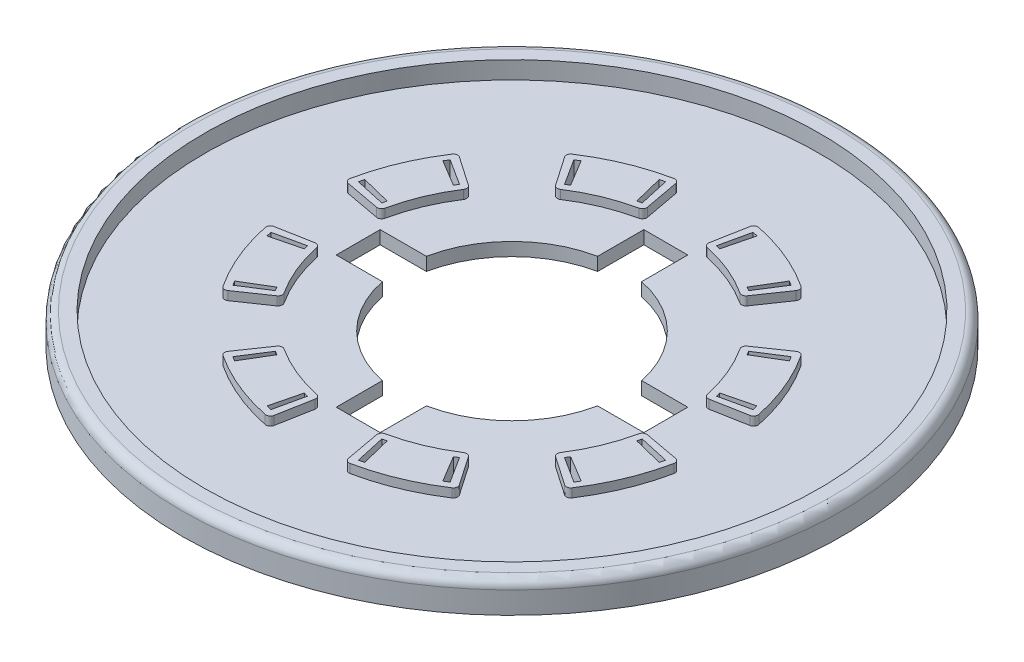
SolidWorks part; units mm, degrees
ref_plane "Alzado" through (0, 0, 0) normal (0, 0, 1) x (1, 0, 0)
ref_plane "Planta" through (0, 0, 0) normal (0, 1, 0) x (1, 0, 0)
ref_plane "Vista lateral" through (0, 0, 0) normal (1, 0, 0) x (0, 0, -1)
sketch "Croquis1" plane through (0, 0, 0) normal (0, 1, 0) x (1, 0, 0)
  circle A0 centre (0, 0) radius 75
  dimension "D1" = 150
extrude "Saliente-Extruir1" add sketch "Croquis1" along normal blind 3
sketch "Croquis3" plane through (0, 3, 0) normal (0, 1, 0) x (1, 0, 0)
  line L0 (-70, 0) -> (70, 0) construction
  line L1 (0, -70) -> (0, 70) construction
  line L3 (-49.4975, -49.4975) -> (49.4975, 49.4975) construction
  line L5 (-49.4975, 49.4975) -> (49.4975, -49.4975) construction
  circle A0 centre (0, 0) radius 75
  circle A1 centre (0, 0) radius 70
  dimension "D1" = 150
  dimension "D2" = 5
extrude "Saliente-Extruir2" add sketch "Croquis3" along normal blind 4
sketch "Croquis7" plane through (0, 3, 0) normal (0, 1, 0) x (1, 0, 0)
  line L0 (51.6188, -52.6795) -> (52.6795, -51.6188)
  line L9 (73.75, -0.75) -> (-73.75, -0.75)
  line L10 (73.75, -0.75) -> (73.75, 0.75)
  line L11 (73.75, 0.75) -> (-73.75, 0.75)
  line L12 (-73.75, -0.75) -> (-73.75, 0.75)
  line L13 (73.75, -0.75) -> (-73.75, 0.75) construction
  line L14 (73.75, 0.75) -> (-73.75, -0.75) construction
  line L15 (51.6188, -52.6795) -> (-52.6795, 51.6188)
  line L16 (-52.6795, 51.6188) -> (-51.6188, 52.6795)
  line L17 (52.6795, -51.6188) -> (-51.6188, 52.6795)
  line L18 (-0.75, -73.75) -> (0.75, -73.75)
  line L19 (-0.75, -73.75) -> (-0.75, 73.75)
  line L20 (-0.75, 73.75) -> (0.75, 73.75)
  line L21 (0.75, -73.75) -> (0.75, 73.75)
  line L22 (-52.6795, -51.6188) -> (-51.6188, -52.6795)
  line L23 (-52.6795, -51.6188) -> (51.6188, 52.6795)
  line L24 (51.6188, 52.6795) -> (52.6795, 51.6188)
  line L25 (-51.6188, -52.6795) -> (52.6795, 51.6188)
  line L26 (-73.75, 0.75) -> (-73.75, -0.75)
  line L27 (-73.75, 0.75) -> (73.75, 0.75)
  line L28 (73.75, 0.75) -> (73.75, -0.75)
  line L29 (-73.75, -0.75) -> (73.75, -0.75)
  point P0 (0, 0)
  point P25 (0, 0)
  dimension "D1" = 1.5
  dimension "D2" = 147.5
  dimension "D3" = 5
sketch "Croquis2" plane through (0, 0, 0) normal (0, -1, 0) x (1, 0, 0)
  line L0 (0, 0) -> (-75, 0) construction
  line L2 (0, 0) -> (-69.291, 28.7013) construction
  circle A0 centre (0, 0) radius 75 construction
  circle A1 centre (-55.4328, 22.961) radius 2.5
  circle A2 centre (-22.961, 55.4328) radius 2.5
  circle A3 centre (22.961, 55.4328) radius 2.5
  circle A4 centre (55.4328, 22.961) radius 2.5
  circle A5 centre (55.4328, -22.961) radius 2.5
  circle A6 centre (22.961, -55.4328) radius 2.5
  circle A7 centre (-22.961, -55.4328) radius 2.5
  circle A8 centre (-55.4328, -22.961) radius 2.5
  point P25 (0, 0)
  dimension "D1" = 5
  dimension "D2" = 60
  dimension "D4" = 22.5
  dimension "D3" = 8
extrude "Saliente-Extruir3" [suppressed] add sketch "Croquis7" along normal blind 1 contours L11 L19 L17 L15 | L11 L12 L9 L10 | L21 L20 L19 L18 | L23 L24 L25 L22 | L15 L16 L17 L0
extrude "Cortar-Extruir1" cut sketch "Croquis2" against normal blind 2
sketch "Croquis4" plane through (0, 0, 0) normal (0, -1, 0) x (1, 0, 0)
  circle A0 centre (0, 0) radius 25
  dimension "D1" = 50
extrude "Cortar-Extruir2" cut sketch "Croquis4" against normal blind 6
sketch "Croquis8" plane through (0, 3, 0) normal (0, 1, 0) x (1, 0, 0)
  line L0 (-45.7108, -8.472) -> (-37.8425, -7.0137)
  line L1 (-38.313, -26.3318) -> (-31.7182, -21.7993)
  line L2 (-38.313, 26.3318) -> (-31.7182, 21.7993)
  line L4 (-45.7108, 8.472) -> (-37.8425, 7.0137)
  line L20 (0, 0) -> (-75, 0) construction
  line L35 (-8.472, 45.7108) -> (-7.0137, 37.8425)
  line L36 (-26.3318, 38.313) -> (-21.7993, 31.7182)
  line L37 (26.3318, 38.313) -> (21.7993, 31.7182)
  line L38 (8.472, 45.7108) -> (7.0137, 37.8425)
  line L39 (45.7108, 8.472) -> (37.8425, 7.0137)
  line L40 (38.313, 26.3318) -> (31.7182, 21.7993)
  line L41 (38.313, -26.3318) -> (31.7182, -21.7993)
  line L42 (45.7108, -8.472) -> (37.8425, -7.0137)
  line L43 (8.472, -45.7108) -> (7.0137, -37.8425)
  line L44 (26.3318, -38.313) -> (21.7993, -31.7182)
  line L45 (-26.3318, -38.313) -> (-21.7993, -31.7182)
  line L46 (-8.472, -45.7108) -> (-7.0137, -37.8425)
  circle A0 centre (0, 0) radius 37.5 construction
  circle A1 centre (0, 0) radius 47.5 construction
  arc A2 (-36.6821, -7.7892) -> (-31.446, -20.4303) centre (0, 0) ccw
  arc A3 (-39.7155, -26.0562) -> (-46.5077, -9.6586) centre (0, 0) cw
  circle A52 centre (0, 0) radius 75 construction
  arc A53 (-38.313, -26.3318) -> (-39.7155, -26.0562) centre (-38.8794, -25.5077) cw
  arc A54 (-31.7182, -21.7993) -> (-31.446, -20.4303) centre (-32.2846, -20.9752) ccw
  arc A55 (-37.8425, -7.0137) -> (-36.6821, -7.7892) centre (-37.6603, -7.997) cw
  arc A56 (-45.7108, -8.472) -> (-46.5077, -9.6586) centre (-45.5285, -9.4552) ccw
  arc A57 (-46.5077, 9.6586) -> (-39.7155, 26.0562) centre (0, 0) cw
  arc A58 (-38.313, 26.3318) -> (-39.7155, 26.0562) centre (-38.8794, 25.5077) ccw
  arc A59 (-45.7108, 8.472) -> (-46.5077, 9.6586) centre (-45.5285, 9.4552) cw
  arc A60 (-31.7182, 21.7993) -> (-31.446, 20.4303) centre (-32.2846, 20.9752) cw
  arc A61 (-31.446, 20.4303) -> (-36.6821, 7.7892) centre (0, 0) ccw
  arc A62 (-37.8425, 7.0137) -> (-36.6821, 7.7892) centre (-37.6603, 7.997) ccw
  arc A63 (-26.0562, 39.7155) -> (-9.6586, 46.5077) centre (0, 0) cw
  arc A64 (-8.472, 45.7108) -> (-9.6586, 46.5077) centre (-9.4552, 45.5285) ccw
  arc A65 (-26.3318, 38.313) -> (-26.0562, 39.7155) centre (-25.5077, 38.8794) cw
  arc A66 (-7.0137, 37.8425) -> (-7.7892, 36.6821) centre (-7.997, 37.6603) cw
  arc A67 (-7.7892, 36.6821) -> (-20.4303, 31.446) centre (0, 0) ccw
  arc A68 (-21.7993, 31.7182) -> (-20.4303, 31.446) centre (-20.9752, 32.2846) ccw
  arc A69 (9.6586, 46.5077) -> (26.0562, 39.7155) centre (0, 0) cw
  arc A70 (26.3318, 38.313) -> (26.0562, 39.7155) centre (25.5077, 38.8794) ccw
  arc A71 (8.472, 45.7108) -> (9.6586, 46.5077) centre (9.4552, 45.5285) cw
  arc A72 (21.7993, 31.7182) -> (20.4303, 31.446) centre (20.9752, 32.2846) cw
  arc A73 (20.4303, 31.446) -> (7.7892, 36.6821) centre (0, 0) ccw
  arc A74 (7.0137, 37.8425) -> (7.7892, 36.6821) centre (7.997, 37.6603) ccw
  arc A75 (39.7155, 26.0562) -> (46.5077, 9.6586) centre (0, 0) cw
  arc A76 (45.7108, 8.472) -> (46.5077, 9.6586) centre (45.5285, 9.4552) ccw
  arc A77 (38.313, 26.3318) -> (39.7155, 26.0562) centre (38.8794, 25.5077) cw
  arc A78 (37.8425, 7.0137) -> (36.6821, 7.7892) centre (37.6603, 7.997) cw
  arc A79 (36.6821, 7.7892) -> (31.446, 20.4303) centre (0, 0) ccw
  arc A80 (31.7182, 21.7993) -> (31.446, 20.4303) centre (32.2846, 20.9752) ccw
  arc A81 (46.5077, -9.6586) -> (39.7155, -26.0562) centre (0, 0) cw
  arc A82 (38.313, -26.3318) -> (39.7155, -26.0562) centre (38.8794, -25.5077) ccw
  arc A83 (45.7108, -8.472) -> (46.5077, -9.6586) centre (45.5285, -9.4552) cw
  arc A84 (31.7182, -21.7993) -> (31.446, -20.4303) centre (32.2846, -20.9752) cw
  arc A85 (31.446, -20.4303) -> (36.6821, -7.7892) centre (0, 0) ccw
  arc A86 (37.8425, -7.0137) -> (36.6821, -7.7892) centre (37.6603, -7.997) ccw
  arc A87 (26.0562, -39.7155) -> (9.6586, -46.5077) centre (0, 0) cw
  arc A88 (8.472, -45.7108) -> (9.6586, -46.5077) centre (9.4552, -45.5285) ccw
  arc A89 (26.3318, -38.313) -> (26.0562, -39.7155) centre (25.5077, -38.8794) cw
  arc A90 (7.0137, -37.8425) -> (7.7892, -36.6821) centre (7.997, -37.6603) cw
  arc A91 (7.7892, -36.6821) -> (20.4303, -31.446) centre (0, 0) ccw
  arc A92 (21.7993, -31.7182) -> (20.4303, -31.446) centre (20.9752, -32.2846) ccw
  arc A93 (-9.6586, -46.5077) -> (-26.0562, -39.7155) centre (0, 0) cw
  arc A94 (-26.3318, -38.313) -> (-26.0562, -39.7155) centre (-25.5077, -38.8794) ccw
  arc A95 (-8.472, -45.7108) -> (-9.6586, -46.5077) centre (-9.4552, -45.5285) cw
  arc A96 (-21.7993, -31.7182) -> (-20.4303, -31.446) centre (-20.9752, -32.2846) cw
  arc A97 (-20.4303, -31.446) -> (-7.7892, -36.6821) centre (0, 0) ccw
  arc A98 (-7.0137, -37.8425) -> (-7.7892, -36.6821) centre (-7.997, -37.6603) ccw
  point P10 (-39.146, -26.9043)
  point P18 (-30.9047, -21.2402)
  point P21 (-36.8721, -6.8338)
  point P24 (-46.7046, -8.6562)
  point P45 (0, 0)
  point P113 (0, 0)
  point P115 (0, 0)
  dimension "D1" = 75
  dimension "D2" = 95
  dimension "D6" = 8
  dimension "D5" = 1
  dimension "D3" = 10.5
  dimension "D4" = 24
extrude "Saliente-Extruir4" add sketch "Croquis8" along normal blind 2
sketch "Croquis10" plane through (0, 5, 0) normal (0, 1, 0) x (1, 0, 0)
  line L0 (-44.9096, -9.9562) -> (-38.0755, -8.4411)
  line L1 (-44.6336, -11.1284) -> (-37.8415, -9.435)
  line L2 (-37.8425, -7.0137) -> (-45.7108, -8.472) construction
  line L3 (0, 0) -> (-43.8843, -18.1775) construction
  line L34 (-39.4297, 23.6918) -> (-33.4295, 20.0865)
  line L35 (-38.796, -24.7158) -> (-32.8923, -20.9547)
  line L36 (-39.4297, -23.6918) -> (-33.4295, -20.0865)
  line L37 (-38.796, 24.7158) -> (-32.8923, 20.9547)
  line L38 (-44.9096, 9.9562) -> (-38.0755, 8.4411)
  line L39 (-44.6336, 11.1284) -> (-37.8415, 9.435)
  line L40 (-11.1284, 44.6336) -> (-9.435, 37.8415)
  line L41 (-9.9562, 44.9096) -> (-8.4411, 38.0755)
  line L42 (-24.7158, 38.796) -> (-20.9547, 32.8923)
  line L43 (-23.6918, 39.4297) -> (-20.0865, 33.4295)
  line L44 (23.6918, 39.4297) -> (20.0865, 33.4295)
  line L45 (24.7158, 38.796) -> (20.9547, 32.8923)
  line L46 (9.9562, 44.9096) -> (8.4411, 38.0755)
  line L47 (11.1284, 44.6336) -> (9.435, 37.8415)
  line L48 (44.6336, 11.1284) -> (37.8415, 9.435)
  line L49 (44.9096, 9.9562) -> (38.0755, 8.4411)
  line L50 (38.796, 24.7158) -> (32.8923, 20.9547)
  line L51 (39.4297, 23.6918) -> (33.4295, 20.0865)
  line L52 (39.4297, -23.6918) -> (33.4295, -20.0865)
  line L53 (38.796, -24.7158) -> (32.8923, -20.9547)
  line L54 (44.9096, -9.9562) -> (38.0755, -8.4411)
  line L55 (44.6336, -11.1284) -> (37.8415, -9.435)
  line L56 (11.1284, -44.6336) -> (9.435, -37.8415)
  line L57 (9.9562, -44.9096) -> (8.4411, -38.0755)
  line L58 (24.7158, -38.796) -> (20.9547, -32.8923)
  line L59 (23.6918, -39.4297) -> (20.0865, -33.4295)
  line L60 (-23.6918, -39.4297) -> (-20.0865, -33.4295)
  line L61 (-24.7158, -38.796) -> (-20.9547, -32.8923)
  line L62 (-9.9562, -44.9096) -> (-8.4411, -38.0755)
  line L63 (-11.1284, -44.6336) -> (-9.435, -37.8415)
  circle A0 centre (0, 0) radius 39 construction
  circle A1 centre (0, 0) radius 46 construction
  arc A2 (-36.6821, -7.7892) -> (-31.446, -20.4303) centre (0, 0) ccw construction
  arc A3 (-46.5077, -9.6586) -> (-39.7155, -26.0562) centre (0, 0) ccw construction
  arc A4 (-38.0755, -8.4411) -> (-37.8415, -9.435) centre (0, 0) ccw
  arc A5 (-44.9096, -9.9562) -> (-44.6336, -11.1284) centre (0, 0) ccw
  arc A37 (-32.8923, -20.9547) -> (-33.4295, -20.0865) centre (0, 0) cw
  arc A38 (-38.796, -24.7158) -> (-39.4297, -23.6918) centre (0, 0) cw
  arc A39 (-38.796, 24.7158) -> (-39.4297, 23.6918) centre (0, 0) ccw
  arc A40 (-32.8923, 20.9547) -> (-33.4295, 20.0865) centre (0, 0) ccw
  arc A41 (-38.0755, 8.4411) -> (-37.8415, 9.435) centre (0, 0) cw
  arc A42 (-44.9096, 9.9562) -> (-44.6336, 11.1284) centre (0, 0) cw
  arc A43 (-9.9562, 44.9096) -> (-11.1284, 44.6336) centre (0, 0) ccw
  arc A44 (-8.4411, 38.0755) -> (-9.435, 37.8415) centre (0, 0) ccw
  arc A45 (-20.9547, 32.8923) -> (-20.0865, 33.4295) centre (0, 0) cw
  arc A46 (-24.7158, 38.796) -> (-23.6918, 39.4297) centre (0, 0) cw
  arc A47 (24.7158, 38.796) -> (23.6918, 39.4297) centre (0, 0) ccw
  arc A48 (20.9547, 32.8923) -> (20.0865, 33.4295) centre (0, 0) ccw
  arc A49 (8.4411, 38.0755) -> (9.435, 37.8415) centre (0, 0) cw
  arc A50 (9.9562, 44.9096) -> (11.1284, 44.6336) centre (0, 0) cw
  arc A51 (44.9096, 9.9562) -> (44.6336, 11.1284) centre (0, 0) ccw
  arc A52 (38.0755, 8.4411) -> (37.8415, 9.435) centre (0, 0) ccw
  arc A53 (32.8923, 20.9547) -> (33.4295, 20.0865) centre (0, 0) cw
  arc A54 (38.796, 24.7158) -> (39.4297, 23.6918) centre (0, 0) cw
  arc A55 (38.796, -24.7158) -> (39.4297, -23.6918) centre (0, 0) ccw
  arc A56 (32.8923, -20.9547) -> (33.4295, -20.0865) centre (0, 0) ccw
  arc A57 (38.0755, -8.4411) -> (37.8415, -9.435) centre (0, 0) cw
  arc A58 (44.9096, -9.9562) -> (44.6336, -11.1284) centre (0, 0) cw
  arc A59 (9.9562, -44.9096) -> (11.1284, -44.6336) centre (0, 0) ccw
  arc A60 (8.4411, -38.0755) -> (9.435, -37.8415) centre (0, 0) ccw
  arc A61 (20.9547, -32.8923) -> (20.0865, -33.4295) centre (0, 0) cw
  arc A62 (24.7158, -38.796) -> (23.6918, -39.4297) centre (0, 0) cw
  arc A63 (-24.7158, -38.796) -> (-23.6918, -39.4297) centre (0, 0) ccw
  arc A64 (-20.9547, -32.8923) -> (-20.0865, -33.4295) centre (0, 0) ccw
  arc A65 (-8.4411, -38.0755) -> (-9.435, -37.8415) centre (0, 0) cw
  arc A66 (-9.9562, -44.9096) -> (-11.1284, -44.6336) centre (0, 0) cw
  point P82 (0, 0)
  dimension "D1" = 1.5
  dimension "D2" = 1.5
  dimension "D3" = 2
  dimension "D4" = 1.5
extrude "Cortar-Extruir3" cut sketch "Croquis10" against normal blind 11
fillet "Redondeo1" radius 2 1 edges at (0, 7, 75)
sketch "Croquis11" plane through (0, 3, 0) normal (0, 1, 0) x (1, 0, 0)
  line L0 (-5, -35) -> (5, -35)
  line L1 (35, -5) -> (-35, -5)
  line L2 (35, -5) -> (35, 5)
  line L3 (35, 5) -> (-35, 5)
  line L4 (-35, -5) -> (-35, 5)
  line L5 (35, -5) -> (-35, 5) construction
  line L6 (35, 5) -> (-35, -5) construction
  line L7 (-5, -35) -> (-5, 35)
  line L8 (-5, 35) -> (5, 35)
  line L9 (5, -35) -> (5, 35)
  point P0 (0, 0)
  point P13 (0, 0)
  dimension "D1" = 70
  dimension "D2" = 10
  dimension "D3" = 2
extrude "Cortar-Extruir4" cut sketch "Croquis11" against normal blind 10 contours L4 L1 L3 | L9 L8 L7 | L2 L3 L1 | L0 L9 L7 region at (0, 3, 20) region at (-20, 3, 0) region at (20, 3, 0) region at (0, 3, -20)
